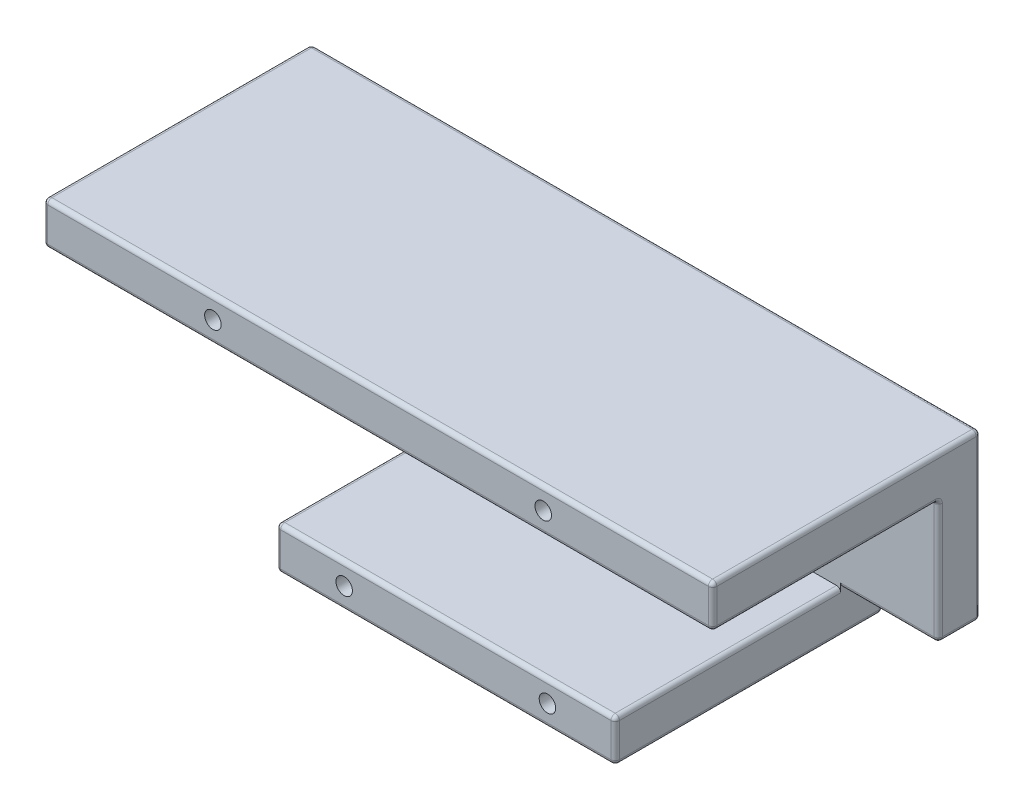
SolidWorks part; units mm, degrees
ref_plane "前视基准面" through (0, 0, 0) normal (0, 0, 1) x (1, 0, 0)
ref_plane "上视基准面" through (0, 0, 0) normal (0, 1, 0) x (1, 0, 0)
ref_plane "右视基准面" through (0, 0, 0) normal (1, 0, 0) x (0, 0, -1)
sketch "草图1" plane through (0, 0, 0) normal (0, 0, 1) x (1, 0, 0)
  line L0 (0, 0) -> (55.5, 0) construction
  line L5 (0, 1.75) -> (55.5, 1.75)
  line L6 (0, -1.75) -> (55.5, -1.75)
  arc A0 (0, 1.75) -> (0, -1.75) centre (0, 0) ccw
  arc A1 (55.5, -1.75) -> (55.5, 1.75) centre (55.5, 0) ccw
  point P4 (27.75, 0)
  dimension "D2" = 1.75
  dimension "D1" = 55.5
extrude "凸台-拉伸3" add sketch "草图1" along normal blind 1.7 contours L5 A1 L6 A0
sketch "草图4" plane through (0, 0, 0) normal (0, 0, -1) x (-1, 0, 0)
  circle A0 centre (0, 0) radius 0.81
  circle A1 centre (-55.5, 0) radius 0.81
  arc A2 (-55.5, 1.75) -> (-55.5, -1.75) centre (-55.5, 0) ccw construction
  dimension "D1" = 1.62
  dimension "D2" = 1.62
extrude "凸台-拉伸4" add sketch "草图4" against normal blind 3.7
sketch "草图5" plane through (0, 0, 0) normal (0, 0, -1) x (-1, 0, 0)
  line L1 (-67, 6.23) -> (12, 6.23)
  line L2 (-67, 6.23) -> (-67, -8.24)
  line L3 (-67, -8.24) -> (12, -8.24)
  line L4 (12, 6.23) -> (12, -8.24)
  dimension "D1" = 12
  dimension "D2" = 14.47
  dimension "D3" = 6.23
  dimension "D4" = 79
extrude "凸台-拉伸5" add sketch "草图5" along normal blind 5 contours L4 L3 L2 L1
sketch "草图6" plane through (0, 6.23, 0) normal (0, 1, 0) x (1, 0, 0)
  line L1 (-12, 5) -> (67, 5)
  line L2 (-12, 5) -> (-12, -26.63)
  line L3 (-12, -26.63) -> (67, -26.63)
  line L4 (67, 5) -> (67, -26.63)
  dimension "D1" = 31.63
extrude "凸台-拉伸6" add sketch "草图6" along normal blind 5
fillet "圆角1" radius 0.31 1 edges at (27.5, 6.23, 0)
fillet "圆角2" radius 0.5 1 edges at (67, -8.24, -2.5)
fillet "圆角3" radius 0.5 1 edges at (-12, -8.24, -2.5)
fillet "圆角5" radius 0.5 1 edges at (67, 11.23, 10.815)
sketch "草图8" plane through (0, -8.24, 0) normal (0, -1, 0) x (-1, 0, 0)
  line L0 (-66.5, 5) -> (11.5, 5) construction
  line L1 (-15.5, -26.63) -> (-55.5, -26.63)
  line L2 (-15.5, -26.63) -> (-15.5, 5)
  line L3 (-15.5, 5) -> (-55.5, 5)
  line L4 (-55.5, -26.63) -> (-55.5, 5)
  line L5 (-55.5, -1.7) -> (-55.5, 0) construction
  line L6 (12, -26.63) -> (-67, -26.63) construction
  dimension "D1" = 40
extrude "凸台-拉伸7" add sketch "草图8" along normal blind 5
fillet "圆角6" radius 0.5 25 edges at (67, 8.48, 26.63) (66.8536, 11.0836, 26.63) (2, -8.24, -5) (-11.8536, -8.0936, -5) (27.25, 11.23, -5) (66.8536, 11.0836, -5) (61, -8.24, -5) (66.8536, -8.0936, -5) (27.5, 6.23, 26.63) (-12, 8.73, 26.63) (27.25, 11.23, 26.63) (-12, 11.23, 10.815) (15.5, -8.24, 13.315) (15.5, -10.74, 26.63) (35.5, -8.24, 26.63) (55.5, -8.24, 13.315) (55.5, -10.74, 26.63) (55.5, -13.24, 10.815) (35.5, -13.24, 26.63) (15.5, -13.24, 10.815) (15.5, -10.74, -5) (-12, 1.745, -5) (55.5, -10.74, -5) (35.5, -13.24, -5) (67, 1.495, -5)
sketch "草图9" plane through (0, 0, 26.63) normal (0, 0, 1) x (1, 0, 0)
  line L1 (15.5, -12.74) -> (15.5, -8.74) construction
  line L2 (55.5, -8.74) -> (55.5, -12.74) construction
  line L3 (67, 10.73) -> (67, 6.23) construction
  line L4 (-12, 6.23) -> (-12, 10.73) construction
  circle A0 centre (23.5, -10.74) radius 0.975
  circle A1 centre (47.5, -10.74) radius 0.975
  circle A2 centre (8, 8.73) radius 0.975
  circle A3 centre (47, 8.73) radius 0.975
  point P21 (67, 8.48)
  dimension "D3" = 1.95
  dimension "D4" = 1.95
  dimension "D9" = 1.95
  dimension "D10" = 1.95
  dimension "D1" = 8
  dimension "D2" = 8
  dimension "D5" = 20
  dimension "D6" = 20
  dimension "D7" = 2.5
  dimension "D8" = 2.5
extrude "切除-拉伸1" cut sketch "草图9" against normal blind 5
fillet "圆角7" radius 0.5 12 edges at (2, -8.24, 0) (-11.8536, -8.0936, 0) (-12, -0.91, 0) (-12, 6.1392, 0.0908) (-11.8536, 6.3764, 26.4836) (66.8536, 6.3764, 26.4836) (61, -8.24, 0) (66.8536, -8.0936, 0) (67, -0.91, 0) (67, 6.1392, 0.0908) (-12, 6.23, 13.22) (67, 6.23, 13.22)
